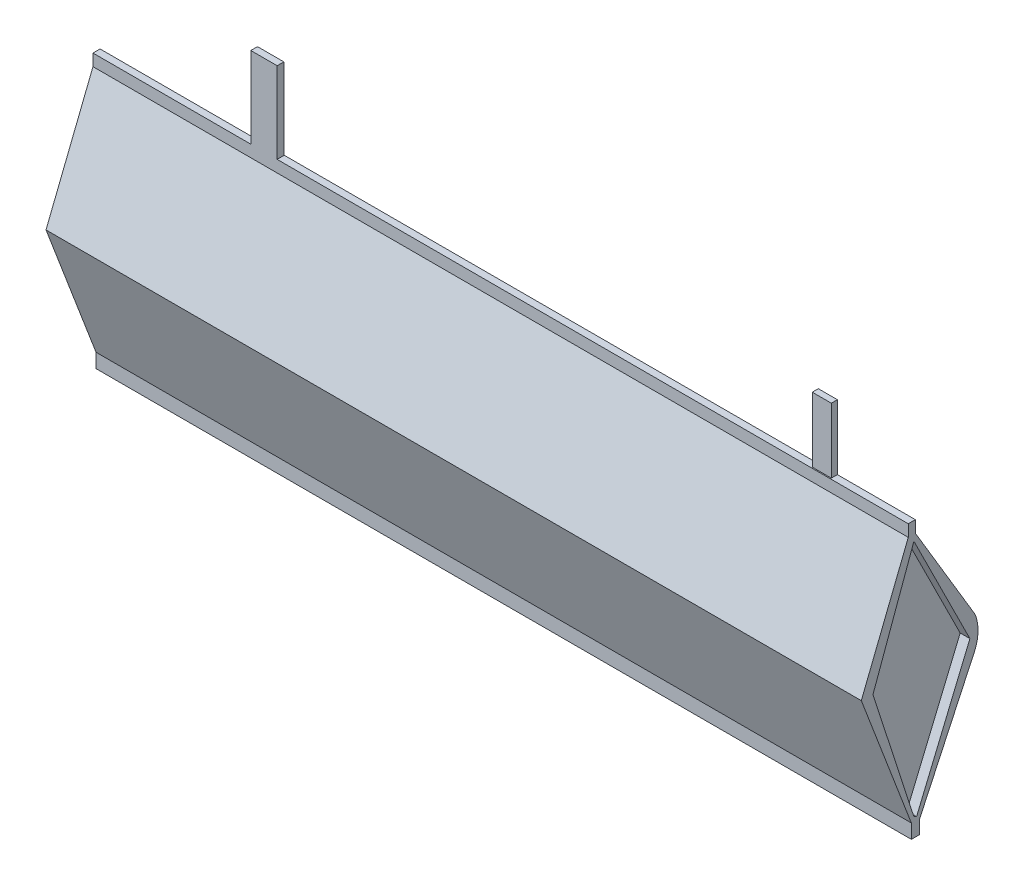
SolidWorks part; units mm, degrees
ref_plane "Front Plane" through (0, 0, 0) normal (0, 0, 1) x (1, 0, 0)
ref_plane "Top Plane" through (0, 0, 0) normal (0, 1, 0) x (1, 0, 0)
ref_plane "Right Plane" through (0, 0, 0) normal (1, 0, 0) x (0, 0, -1)
sketch "Sketch4" plane through (0, 0, 0) normal (0, 0, 1) x (1, 0, 0)
  line L1 (-31.4181, 42.3611) -> (31.4181, 42.3611)
  line L2 (-31.4181, 42.3611) -> (-31.4181, -42.3611)
  line L3 (-31.4181, -42.3611) -> (31.4181, -42.3611)
  line L4 (31.4181, 42.3611) -> (31.4181, -42.3611)
  line L5 (-31.4181, 42.3611) -> (31.4181, -42.3611) construction
  line L6 (-31.4181, -42.3611) -> (31.4181, 42.3611) construction
  point P0 (0, 0)
extrude "Boss-Extrude2" add sketch "Sketch4" along normal blind 50
sketch "Sketch5" plane through (31.4181, 0, 0) normal (1, 0, 0) x (0, 0, -1)
  line L0 (-31.846, 42.3611) -> (-33.6642, 67.8538)
  line L1 (-50, 42.3611) -> (0, 42.3611) construction
  line L2 (-46.3223, 2.3889) -> (-30.8984, -37.9824)
  line L3 (-30.8984, -37.9824) -> (-30.8984, -42.3611)
  line L4 (-50, -42.3611) -> (0, -42.3611) construction
  line L6 (-29.0687, -42.3611) -> (-29.0687, -37.9824)
  line L7 (-29.0687, -37.9824) -> (-13.2397, 2.3889)
  line L8 (-13.2397, 2.3889) -> (-28.1509, 38.7282)
  line L9 (-28.1509, 38.7282) -> (-28.1509, 42.3611)
  line L11 (-31.846, 42.3611) -> (-31.846, 38.7282)
  line L12 (-31.846, 38.7282) -> (-46.3223, 2.3889)
  line L13 (-33.6642, 67.8538) -> (-71.791, 67.8538)
  line L14 (-71.791, 67.8538) -> (-78.4638, -46.7769)
  line L15 (-78.4638, -46.7769) -> (-30.8035, -45.1607)
  line L16 (-30.8035, -45.1607) -> (-30.8984, -42.3611)
  line M12 (0, 42.3611) -> (-50, 42.3611)
  line M13 (-50, 42.3611) -> (-50, -42.3611)
  line M14 (-50, -42.3611) -> (0, -42.3611)
extrude "Cut-Extrude2" cut sketch "Sketch5" against normal blind 80 contours L12 L11 L3 L2 M12 M13 M14
sketch "Sketch6" plane through (31.4181, 0, 0) normal (1, 0, 0) x (0, 0, -1)
  line L0 (-29.6554, 42.3611) -> (-29.6554, 38.7226)
  line L1 (-31.846, 42.3611) -> (0, 42.3611) construction
  line L2 (-29.6554, 38.7226) -> (-8.7764, 3.7502)
  line L3 (-8.7764, 3.7502) -> (-28.3285, -38.1177)
  line L4 (-28.3285, -38.1177) -> (-28.3285, -42.3611)
  line L5 (-30.8984, -42.3611) -> (0, -42.3611) construction
  line L6 (-28.3285, -42.3611) -> (-27.6775, -46.6259)
  line L7 (-27.6775, -46.6259) -> (16.8398, -52.0454)
  line L8 (16.8398, -52.0454) -> (10.2677, 27.1903)
  line L9 (10.2677, 27.1903) -> (3.7395, 54.484)
  line L10 (3.7395, 54.484) -> (-29.6554, 42.3611)
extrude "Cut-Extrude3" cut sketch "Sketch6" against normal blind 80
sketch "Sketch7" plane through (-31.4181, 0, 0) normal (-1, 0, 0) x (0, 0, 1)
  line L1 (29.6554, 38.7226) -> (8.7764, 3.7502) construction
  line L2 (8.7764, 3.7502) -> (28.3285, -38.1177) construction
  arc A0 (13.2289, 11.2081) -> (11.7109, -2.5336) centre (22.9458, 3.18) ccw
  arc A1 (13.2289, 11.2081) -> (11.7109, -2.5336) centre (8.6224, 4.7623) ccw
extrude "Cut-Extrude5" cut sketch "Sketch7" against normal blind 80
sketch "Sketch8" plane through (31.4181, 0, 0) normal (1, 0, 0) x (0, 0, -1)
  line L0 (-30.1116, 36.8174) -> (-42.7351, 2.196)
  line L1 (-42.7351, 2.196) -> (-30.1116, -36.6941)
  line L2 (-30.1116, -36.6941) -> (-29.2891, -37.0782)
  line L3 (-29.2891, -37.0782) -> (-12.8456, 2.196)
  line L4 (-12.8456, 2.196) -> (-30.1116, 36.8174)
extrude "Cut-Extrude6" cut sketch "Sketch8" against normal blind 3
sketch "Sketch9" plane through (0, 0, 29.6554) normal (0, 0, -1) x (-1, 0, 0)
  line L0 (19.8699, 42.3611) -> (19.8699, 38.7226)
  line L1 (31.4181, 42.3611) -> (-31.4181, 42.3611) construction
  line L2 (31.4181, 38.7226) -> (-31.4181, 38.7226) construction
  line L3 (19.8699, 38.7226) -> (19.8699, 5.587)
  line L4 (19.8699, 5.587) -> (19.8699, -4.1869)
  line L5 (19.8699, -4.1869) -> (19.8699, -38.2085)
  line L6 (19.8699, -38.2085) -> (19.8699, -42.0598)
  line L7 (19.8699, -42.0598) -> (19.8699, -47.0269)
  line L8 (19.8699, -47.0269) -> (41.2567, -49.5859)
  line L9 (41.2567, -49.5859) -> (42.0813, -21.1977)
  line L10 (42.0813, -21.1977) -> (42.0813, 12.4282)
  line L11 (42.0813, 12.4282) -> (37.4822, 37.5131)
  line L12 (37.4822, 37.5131) -> (31.4181, 49.4838)
  line L13 (31.4181, 49.4838) -> (19.8699, 42.3611)
extrude "Cut-Extrude8" cut sketch "Sketch9" against normal blind 80
sketch "Sketch10" plane through (0, -2.8774, 4.8197) normal (0, 0.5126, -0.8586) x (-1, 0, 0)
  line L0 (19.8699, 48.4497) -> (25.6937, -39.8033)
  line L1 (25.6937, -39.8033) -> (32.4481, -43.4448)
  line L2 (32.4481, -43.4448) -> (49.8026, -43.4448)
  line L3 (49.8026, -43.4448) -> (32.4481, 57.8409)
  line L4 (32.4481, 57.8409) -> (19.8699, 48.4497)
extrude "Cut-Extrude9" cut sketch "Sketch10" against normal blind 80
sketch "Sketch11" plane through (0, 42.3611, 0) normal (0, 1, 0) x (1, 0, 0)
  line L0 (-19.8699, -29.6554) -> (31.4181, -29.6554) construction
  line L1 (7.3729, -31.5211) -> (1.502, -31.5211)
  line L2 (7.3729, -31.5211) -> (7.3729, -29.6554)
  line L3 (7.3729, -29.6554) -> (1.502, -29.6554)
  line L4 (1.502, -31.5211) -> (1.502, -29.6554)
  line L5 (7.3729, -31.5211) -> (1.502, -29.6554) construction
  line L6 (7.3729, -29.6554) -> (1.502, -31.5211) construction
  point P0 (4.4374, -30.5883)
extrude "Boss-Extrude3" add sketch "Sketch11" along normal blind 20
scale "Scale1" scale about centroid uniform scaling yes scale factor 0.5
scale "Scale2" scale about centroid uniform scaling yes scale factor 0.4
scale "Scale3" scale about centroid uniform scaling yes scale factor 0.5
scale "Scale4" scale about centroid uniform scaling yes scale factor 1
scale "Scale5" scale about centroid uniform scaling yes scale factor 4
sketch "Sketch14" plane through (-5.5213, 0, 0) normal (-1, 0, 0) x (0, 0, 1)
  line L0 (28.9061, 17.5056) -> (29.7823, 17.5056)
  line L1 (29.7823, 17.5056) -> (29.7823, 16.0525)
  line L2 (35.5728, 1.5168) -> (29.7823, 16.0525) construction
  line L3 (29.7823, 16.0525) -> (29.7823, 17.5056) construction
  line L4 (29.7823, 16.0525) -> (35.5728, 1.5168)
  line L5 (35.5728, 1.5168) -> (29.4033, -14.6318)
  line L6 (29.4033, -14.6318) -> (29.4033, -16.3833)
  line L7 (29.4033, -16.3833) -> (28.0872, -16.3833)
  line L8 (28.0872, -16.3833) -> (28.1159, -14.6861)
  line L9 (28.1159, -14.6861) -> (21.4083, -0.1411)
  line L10 (21.4083, -0.1411) -> (21.122, 0.7991)
  line L11 (21.122, 0.7991) -> (21.0248, 1.7842)
  line L12 (21.0248, 1.7842) -> (21.122, 2.7891)
  line L13 (21.122, 2.7891) -> (21.4142, 3.7322)
  line L14 (21.4142, 3.7322) -> (28.9061, 16.0502)
  line L15 (28.9061, 16.0502) -> (28.9061, -16.3833) construction
  line L16 (28.9061, 17.5056) -> (28.9061, 16.0502) construction
  line L17 (28.9061, 16.0502) -> (28.9061, 17.5056)
extrude "Boss-Extrude5" add sketch "Sketch14" along normal blind 80
sketch "Sketch15" plane through (0, 17.5056, 0) normal (0, 1, 0) x (1, 0, 0)
  line L0 (-85.5213, -29.7823) -> (14.9939, -29.7823) construction
  line L1 (-66.0647, -28.9556) -> (-62.8147, -28.9556)
  line L2 (-66.0647, -28.9556) -> (-66.0647, -29.7823)
  line L3 (-66.0647, -29.7823) -> (-62.8147, -29.7823)
  line L4 (-62.8147, -28.9556) -> (-62.8147, -29.7823)
  line L5 (-66.0647, -28.9556) -> (-62.8147, -29.7823) construction
  line L6 (-66.0647, -29.7823) -> (-62.8147, -28.9556) construction
  point P0 (-64.4397, -29.369)
extrude "Boss-Extrude6" add sketch "Sketch15" along normal blind 10
